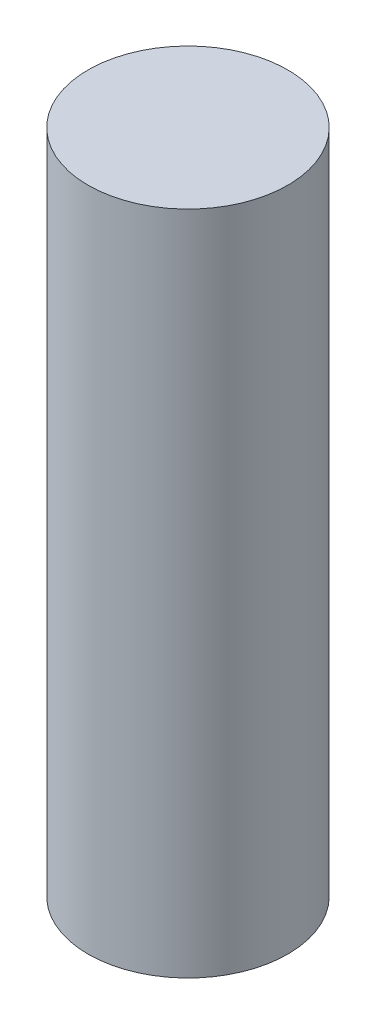
SolidWorks part; units mm, degrees
ref_plane "Front Plane" through (0, 0, 0) normal (0, 0, 1) x (1, 0, 0)
ref_plane "Top Plane" through (0, 0, 0) normal (0, 1, 0) x (1, 0, 0)
ref_plane "Right Plane" through (0, 0, 0) normal (1, 0, 0) x (0, 0, -1)
sketch "Sketch1" plane through (0, 0, 0) normal (0, 1, 0) x (1, 0, 0)
  circle A0 centre (0, 0) radius 15
  dimension "D1" = 30
extrude "Boss-Extrude1" add sketch "Sketch1" along normal blind 100
